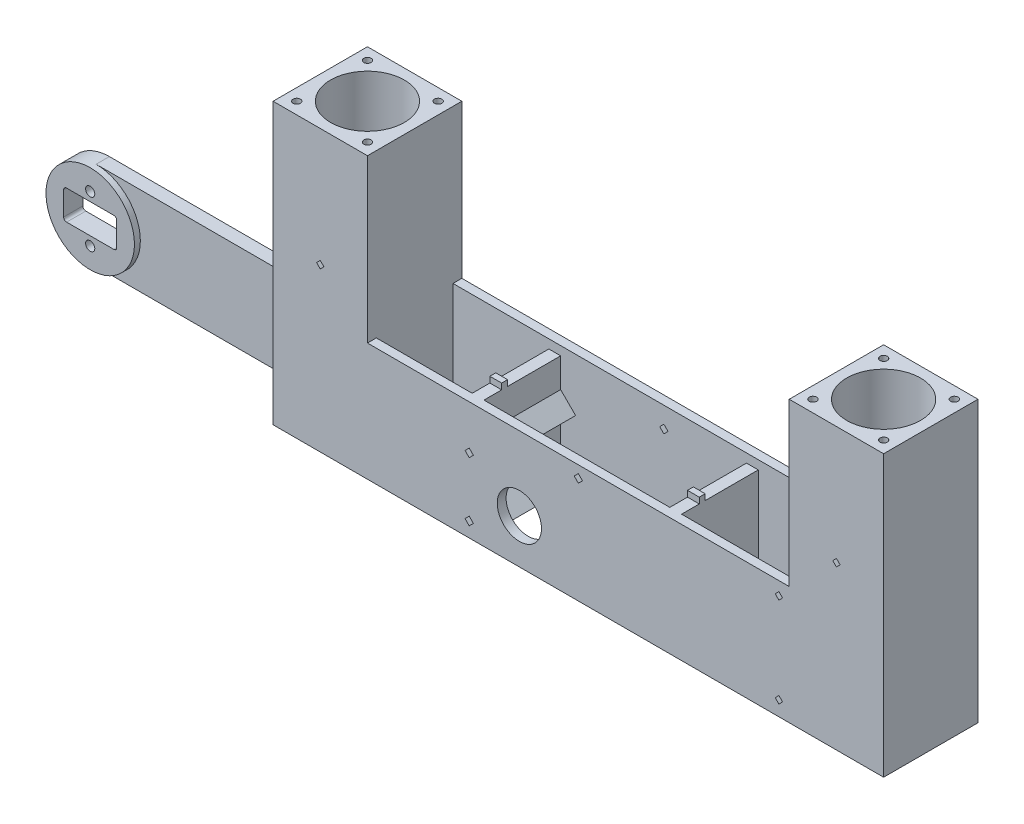
SolidWorks part; units mm, degrees
material "ABS PC"
ref_plane "Ebene vorne" through (0, 0, 0) normal (0, 0, 1) x (1, 0, 0)
ref_plane "Ebene oben" through (0, 0, 0) normal (0, 1, 0) x (1, 0, 0)
ref_plane "Ebene rechts" through (0, 0, 0) normal (1, 0, 0) x (0, 0, -1)
sketch "Skizze1" plane through (0, 0, 0) normal (0, 1, 0) x (1, 0, 0)
  line L0 (-269.7917, 0) -> (290.9722, 0) construction
  line L1 (0, 162.6736) -> (0, -161.9792) construction
  line L2 (-103.5, -16) -> (-103.5, 16)
  line L3 (-103.5, 16) -> (103.5, 16)
  line L4 (-103.5, -16) -> (103.5, -16)
  line L5 (103.5, -16) -> (103.5, 16)
  circle A0 centre (-87.5, 0) radius 9.5
  circle A1 centre (87.5, 0) radius 9.5
  point P5 (103.5, 0)
  point P10 (-103.5, 0)
  point P12 (0, -16)
  point P13 (0, 16)
  dimension "D4" = 19
  dimension "D1" = 16
  dimension "D2" = 32
  dimension "D3" = 175
extrude "Aufsatz-Linear austragen1" add sketch "Skizze1" along normal blind 80 and the other way blind 15
sketch "Skizze2" plane through (0, 80, 0) normal (0, 1, 0) x (1, 0, 0)
  circle A0 centre (-87.5, 0) radius 12.5
  circle A1 centre (87.5, 0) radius 12.5
  dimension "D1" = 25
extrude "Schnitt-Linear austragen1" cut sketch "Skizze2" against normal blind 31
sketch "Skizze3" plane through (0, -15, 0) normal (0, -1, 0) x (1, 0, 0)
  circle A0 centre (-87.5, 0) radius 12.5
  circle A1 centre (87.5, 0) radius 12.5
  dimension "D1" = 25
extrude "Schnitt-Linear austragen2" cut sketch "Skizze3" against normal blind 31
sketch "Skizze4" plane through (0, 0, 0) normal (0, 0, 1) x (1, 0, 0)
  line L0 (-149.1932, 0) -> (124.6611, 0) construction
  line L1 (-20, 118.7837) -> (-20, -125.6424) construction
  line L2 (-38.4142, 10) -> (-37, 11.4142)
  line L3 (-37, 11.4142) -> (-35.5858, 10)
  line L4 (-35.5858, 10) -> (-37, 8.5858)
  line L5 (-37, 8.5858) -> (-38.4142, 10)
  line L6 (-37, 16.4098) -> (-37, 4.3215) construction
  line L7 (-35.5858, -10) -> (-37, -8.5858)
  line L8 (-37, -8.5858) -> (-38.4142, -10)
  line L9 (-38.4142, -10) -> (-37, -11.4142)
  line L10 (-37, -11.4142) -> (-35.5858, -10)
  circle A1 centre (-37, 10) radius 1 construction
  circle A2 centre (-37, -10) radius 1 construction
  circle A4 centre (-20, 0) radius 7.5
  dimension "D3" = 15
  dimension "D4" = 2
  dimension "D1" = 20
  dimension "D2" = 17
  dimension "D5" = 20
extrude "Schnitt-Linear austragen3" cut sketch "Skizze4" against normal blind 5 and the other way through all
ref_axis "Achse1" through (0, 0, 17.6) along (0, 0, -1)
sketch "Skizze6" plane through (0, 0, 16) normal (0, 0, 1) x (1, 0, 0)
  line L0 (0, 146.2743) -> (0, -100.8814) construction
  line L1 (-208.928, 0) -> (145.5561, 0) construction
  line L2 (-71.5, 80) -> (-71.5, 25)
  line L3 (-103.5, 80) -> (103.5, 80) construction
  line L4 (-71.5, 25) -> (71.5, 25)
  line L5 (-71.5, 80) -> (71.5, 80)
  line L6 (71.5, 80) -> (71.5, 25)
  line L7 (103.5, -15) -> (103.5, 80) construction
  point P12 (0, 80)
  point P13 (0, 25)
  dimension "D1" = 32
  dimension "D2" = 55
extrude "Schnitt-Linear austragen5" cut sketch "Skizze6" against normal through all
sketch "Skizze5" plane through (0, 0, 0) normal (0, 0, -1) x (-1, 0, 0)
  line L0 (430.7354, 0) -> (-150.871, 0) construction
  line L1 (0, 127.9539) -> (0, -79.2962) construction
  line L6 (180, 15) -> (103.5, 15)
  line L7 (103.5, -15) -> (103.5, 15)
  line L9 (180, -15) -> (103.5, -15)
  line L10 (180, 8) -> (180, -8) construction
  line L15 (103.5, -15) -> (103.5, 80) construction
  line L16 (171, -4) -> (171, 4)
  line L17 (172, 5) -> (188, 5)
  line L18 (172, -5) -> (188, -5)
  line L22 (189, -4) -> (189, 4)
  circle A4 centre (180, 8) radius 1.55
  circle A5 centre (180, -8) radius 1.55
  arc A12 (172, -5) -> (171, -4) centre (172, -4) cw
  arc A13 (171, 4) -> (172, 5) centre (172, 4) cw
  arc A16 (189, 4) -> (188, 5) centre (188, 4) ccw
  arc A17 (188, -5) -> (189, -4) centre (188, -4) ccw
  arc A18 (180, 15) -> (180, -15) centre (180, 0) cw
  point P14 (171, 0)
  point P16 (300, 0)
  point P20 (171, -5)
  point P24 (171, 5)
  point P28 (194.1421, -5)
  point P29 (180, 5)
  point P31 (194.1421, 5)
  point P37 (180, -5)
  dimension "D3" = 3.1
  dimension "D6" = 1
  dimension "D7" = 18
  dimension "D1" = 9
  dimension "D2" = 10
  dimension "D4" = 16
  dimension "D5" = 180
extrude "Aufsatz-Linear austragen2" add sketch "Skizze5" along normal blind 5 and the other way blind 1.5
sketch "Skizze8" plane through (0, 25, 0) normal (0, 1, 0) x (1, 0, 0)
  line L0 (-71.5, -13) -> (-71.5, 13)
  line L1 (-71.5, 16) -> (-71.5, -16) construction
  line L3 (71.5, 16) -> (71.5, -16) construction
  line L4 (71.5, 13) -> (71.5, -13)
  line L5 (71.5, -13) -> (32, -13)
  line L7 (-71.5, -16) -> (71.5, -16) construction
  line L10 (-71.5, 13) -> (28, 13)
  line L17 (-71.5, 16) -> (71.5, 16) construction
  line L18 (28, 13) -> (28, -13)
  line L19 (32, 13) -> (32, -13)
  line L20 (32, 13) -> (71.5, 13)
  line L21 (28, -13) -> (-71.5, -13)
  line L22 (30, 25.3355) -> (30, -20.738) construction
  dimension "D1" = 3
  dimension "D2" = 3
  dimension "D7" = 30
  dimension "D8" = 4
extrude "Schnitt-Linear austragen6" cut sketch "Skizze8" against normal through all and the other way through all
hole_wizard "Ø2.5 (2.5) Durchmesser Bohrung2" positions "Skizze10" profile "Skizze9" hole size "Ø2.5" standard "ANSI Metrisch"
sketch "Skizze10" plane through (0, 80, 0) normal (0, 1, 0) x (1, 0, 0)
  line L0 (87.5, 0) -> (48.7157, -38.7843) construction
  line L3 (124.0826, 0) -> (39.2882, 0) construction
  line L6 (87.5, -22.16) -> (87.5, 22.9374) construction
  line L9 (0, -38.7843) -> (0, 32.4108) construction
  circle A0 centre (87.5, 0) radius 16.955 construction
  point P0 (75.511, -11.989)
  point P25 (99.489, -11.989)
  point P28 (75.511, 11.989)
  point P29 (99.489, 11.989)
  point P36 (-75.511, 11.989)
  point P37 (-99.489, 11.989)
  point P38 (-75.511, -11.989)
  point P39 (-99.489, -11.989)
  dimension "D2" = 33.91
  dimension "D1" = 45
sketch "Skizze9" plane through (75.511, 80, 11.989) normal (1, 0, 0) x (0, 0, 1)
  line L0 (0, 0) -> (0, 11.25)
  line L1 (0, 11.25) -> (1.25, 10)
  line L2 (1.25, 10) -> (1.25, 0)
  line L5 (1.25, 0) -> (0, 0)
  line L10 (0, 11.25) -> (-1.25, 10) construction
  line L11 (0, -6.35) -> (0, 107.95) construction
  dimension "Bohrerdurchmesser" = 2.5
  dimension "Bohrungstiefe" = 10
  dimension "Spitzenwinkel" = 90
hole_wizard "Ø2.5 (2.5) Durchmesser Bohrung1" positions "Skizze12" profile "Skizze11" hole size "Ø2.5" standard "ANSI Metrisch"
sketch "Skizze12" plane through (0, -15, 0) normal (0, -1, 0) x (-1, 0, 0)
  point P0 (-75.511, 11.989)
  point P4 (-99.489, 11.989)
  point P7 (-99.489, -11.989)
  point P10 (-75.511, -11.989)
  point P13 (75.511, 11.989)
  point P16 (99.489, 11.989)
  point P19 (75.511, -11.989)
  point P22 (99.489, -11.989)
sketch "Skizze11" plane through (75.511, -15, -11.989) normal (1, 0, 0) x (0, 0, -1)
  line L0 (0, 0) -> (0, 11.25)
  line L1 (0, 11.25) -> (1.25, 10)
  line L2 (1.25, 10) -> (1.25, 0)
  line L5 (1.25, 0) -> (0, 0)
  line L10 (0, 11.25) -> (-1.25, 10) construction
  line L11 (0, -6.35) -> (0, 107.95) construction
  dimension "Bohrerdurchmesser" = 2.5
  dimension "Bohrungstiefe" = 10
  dimension "Spitzenwinkel" = 90
sketch "Skizze13" plane through (0, 0, 1.5) normal (0, 0, 1) x (1, 0, 0)
  line L0 (-180, 15) -> (-103.5, 15)
  line L1 (-103.5, 15) -> (-103.5, -15)
  line L2 (-103.5, 15) -> (-103.5, -15) construction
  line L3 (-103.5, -15) -> (-180, -15)
  line L4 (-430.7354, 0) -> (150.871, 0) construction
  line L5 (-180, 8) -> (-180, -8) construction
  circle A0 centre (-180, 0) radius 15 construction
  arc A2 (-180, 15) -> (-180, -15) centre (-180, 0) cw
extrude "Schnitt-Linear austragen7" cut sketch "Skizze13" against normal blind 2
sketch "Skizze14" plane through (-103.5, 0, 0) normal (-1, 0, 0) x (0, 0, 1)
  line L0 (-5, 25.9725) -> (-5, -25.9828) construction
  line L1 (-5, 15) -> (-5, -15) construction
  line L2 (-29.6836, 0) -> (26.6798, 0) construction
  line L7 (-5, -15) -> (-13.5, -15)
  line L8 (-16, -15) -> (-5, -15) construction
  line L9 (-13.5, -15) -> (-13.5, -7.2218)
  line L10 (-13.5, -7.2218) -> (-5, 1.2782)
  line L14 (-5, 1.2228) -> (-5, 1.2782)
  line L15 (-5, 1.2228) -> (-5, -15)
  line L16 (-10.6213, -7.8787) -> (-8.5, -5.7574)
  line L17 (-8.5, -5.7574) -> (-6.3787, -7.8787)
  line L18 (-8.5, -3.3727) -> (-8.5, -14.5096) construction
  circle A0 centre (-8.5, -10) radius 3 construction
  arc A2 (-10.6213, -7.8787) -> (-6.3787, -7.8787) centre (-8.5, -10) ccw
  dimension "D1" = 6
  dimension "D3" = 6
  dimension "D2" = 3.5
  dimension "D4" = 5
  dimension "D5" = 2.5
  dimension "D6" = 5
extrude "Aufsatz-Linear austragen3" add sketch "Skizze14" along normal up to surface (67.5 mm away) up to face at (-171, 0, -1.75)
sketch "Skizze15" plane through (0, 0, 16) normal (0, 0, 1) x (1, 0, 0)
  line L0 (68, 28.7814) -> (68, -61.0594) construction
  line L1 (48.6724, 20.5) -> (91.1875, 20.5) construction
  line L2 (53.6221, -10) -> (105.5391, -10) construction
  line L3 (66.75, 20.5) -> (68, 21.75)
  line L4 (68, 21.75) -> (69.25, 20.5)
  line L5 (69.25, 20.5) -> (68, 19.25)
  line L6 (68, 19.25) -> (66.75, 20.5)
  line L7 (68, -8.75) -> (69.25, -10)
  line L8 (69.25, -10) -> (68, -11.25)
  line L9 (68, -11.25) -> (66.75, -10)
  line L10 (66.75, -10) -> (68, -8.75)
  circle A0 centre (68, 20.5) radius 0.8839 construction
  circle A1 centre (68, 20.5) radius 1.25 construction
  dimension "D1" = 2.5
  dimension "D2" = 30.5
  dimension "D3" = 68
  dimension "D4" = 10
extrude "Schnitt-Linear austragen8" cut sketch "Skizze15" against normal blind 12
sketch "Skizze17" plane through (0, 0, -16) normal (0, 0, -1) x (-1, 0, 0)
  line L0 (37, 35.0754) -> (37, -31.7967) construction
  line L5 (37, 11.4142) -> (35.5858, 10)
  line L6 (-12.0484, 0) -> (67.2754, 0) construction
  line L11 (39, 25) -> (35, 25)
  line L12 (71.5, 25) -> (-71.5, 25) construction
  line L13 (35, 25) -> (35, 15.0711)
  line L14 (35, 15.0711) -> (29.9289, 10)
  line L15 (29.9289, 10) -> (35, 4.9289)
  line L16 (35, 4.9289) -> (35, -4.9289)
  line L17 (35, -4.9289) -> (29.9289, -10)
  line L18 (29.9289, -10) -> (35, -15.0711)
  line L19 (35, -15.0711) -> (35, -15)
  line L20 (-103.5, -15) -> (103.5, -15) construction
  line L21 (35, -15) -> (39, -15)
  line L22 (39, 25) -> (39, 15.0711)
  line L23 (39, 15.0711) -> (44.0711, 10)
  line L24 (44.0711, 10) -> (39, 4.9289)
  line L25 (39, 4.9289) -> (39, -4.9289)
  line L26 (39, -4.9289) -> (44.0711, -10)
  line L27 (44.0711, -10) -> (39, -15.0711)
  line L28 (39, -15.0711) -> (39, -15)
  line L29 (35.5858, 10) -> (37, 8.5858)
  line L30 (37, 8.5858) -> (38.4142, 10)
  line L31 (38.4142, 10) -> (37, 11.4142)
  line L32 (37, -8.5858) -> (38.4142, -10)
  line L33 (35.5858, -10) -> (37, -8.5858)
  line L34 (38.4142, -10) -> (37, -11.4142)
  line L35 (37, -11.4142) -> (35.5858, -10)
  circle A0 centre (37, 10) radius 1 construction
  circle A1 centre (37, -10) radius 1 construction
  circle A3 centre (37, -10) radius 5 construction
  circle A4 centre (37, 10) radius 5 construction
  point P38 (37, 25)
  point P45 (37, -15)
  dimension "D1" = 2
  dimension "D2" = 10
  dimension "D3" = 4
extrude "Aufsatz-Linear austragen4" add sketch "Skizze17" against normal up to surface (29 mm away) up to face at (-37, -10, 13)
sketch "Skizze18" plane through (0, 0, -16) normal (0, 0, -1) x (-1, 0, 0)
  line L0 (37, 38.0798) -> (37, -28.677) construction
  line L1 (37, 35.0754) -> (37, -31.7967) construction
  line L2 (20.143, 0) -> (52.8328, 0) construction
  line L3 (24.6418, 10) -> (49.3701, 10) construction
  line L4 (32.8988, 10) -> (37, 14.1012)
  line L5 (41.1012, 10) -> (37, 14.1012)
  line L6 (41.1012, 10) -> (37, 5.8988)
  line L7 (32.8988, 10) -> (37, 5.8988)
  line L8 (32.8988, -10) -> (37, -5.8988)
  line L9 (41.1012, -10) -> (37, -5.8988)
  line L10 (41.1012, -10) -> (37, -14.1012)
  line L11 (32.8988, -10) -> (37, -14.1012)
  circle A0 centre (37, 10) radius 2.9 construction
  dimension "D1" = 5.8
extrude "Schnitt-Linear austragen9" cut sketch "Skizze18" against normal offset from surface (26 mm away) 6 up to face at (68, 20.5, 16)
fillet "Verrundung1" radius 10 2 edges at (-103.5, 15, -2.75) (-103.5, 0, -0.5)
sketch "Skizze20" plane through (0, 25, 0) normal (0, 1, 0) x (1, 0, 0)
  line L0 (-71.5, 16) -> (-71.5, 13)
  line L1 (-71.5, 13) -> (71.5, 13)
  line L2 (71.5, 13) -> (71.5, 16)
  line L3 (71.5, 16) -> (-71.5, 16)
extrude "Aufsatz-Linear austragen5" add sketch "Skizze20" along normal blind 3
sketch "Skizze21" plane through (0, 0, 16) normal (0, 0, 1) x (1, 0, 0)
  line L0 (0, 76.3243) -> (0, -37.1528) construction
  line L1 (-55.4701, 0) -> (69.3873, 0) construction
  line L2 (-12.5291, 21) -> (4.7013, 21) construction
  line L3 (0, 22.4142) -> (-1.4142, 21)
  line L4 (-1.4142, 21) -> (0, 19.5858)
  line L5 (0, 19.5858) -> (1.4142, 21)
  line L6 (1.4142, 21) -> (0, 22.4142)
  circle A0 centre (0, 21) radius 1 construction
  dimension "D1" = 2
  dimension "D2" = 21
extrude "Schnitt-Linear austragen10" cut sketch "Skizze21" against normal through all
sketch "Skizze22" plane through (0, 0, 0) normal (0, 0, 1) x (1, 0, 0)
  line L0 (-87.5, 100.8359) -> (-87.5, -46.9125) construction
  line L1 (160.9855, 0) -> (-213.0178, 0) construction
  line L2 (-87.5, 49) -> (-87.5, 80) construction
  line L3 (-87.5, 41.25) -> (-88.75, 40)
  line L4 (-88.75, 40) -> (-87.5, 38.75)
  line L5 (-87.5, 38.75) -> (-86.25, 40)
  line L6 (-86.25, 40) -> (-87.5, 41.25)
  line L7 (87.5, 41.25) -> (86.25, 40)
  line L8 (87.5, 16) -> (87.5, 49) construction
  line L9 (86.25, 40) -> (87.5, 38.75)
  line L10 (87.5, 38.75) -> (88.75, 40)
  line L11 (88.75, 40) -> (87.5, 41.25)
  circle A0 centre (-87.5, 40) radius 1.25 construction
  circle A1 centre (87.5, 40) radius 1.25 construction
  dimension "D1" = 2.5
  dimension "D2" = 40
extrude "Schnitt-Linear austragen11" cut sketch "Skizze22" along normal through all
fillet "Verrundung2" radius 2.5 2 edges at (-37, -14.1012, -3) (-37, 5.8988, -3)
sketch "Skizze23" plane through (0, 25, 0) normal (0, 1, 0) x (1, 0, 0)
  line L0 (-39, -13) -> (-39, 13) construction
  line L1 (-39, -5) -> (-35, -5)
  line L2 (-39, -5) -> (-39, -7)
  line L3 (-39, -7) -> (-35, -7)
  line L4 (-35, -5) -> (-35, -7)
  line L5 (-35, -13) -> (-35, 13) construction
  line L6 (28, 13) -> (28, -13) construction
  line L7 (28, -5) -> (32, -5)
  line L8 (28, -5) -> (28, -7)
  line L9 (28, -7) -> (32, -7)
  line L10 (32, -5) -> (32, -7)
  line L11 (32, -13) -> (32, 13) construction
  dimension "D1" = 5
  dimension "D2" = 2
extrude "Aufsatz-Linear austragen6" add sketch "Skizze23" along normal blind 2
ref_axis "Achse2" through (-210.9831, 0, 0) along (1, 0, 0)
ref_axis "Achse3" through (0, 0, -17.6) along (0, 0, 1)
ref_axis "Achse4" through (0, 131.005, 0) along (0, -1, 0)
